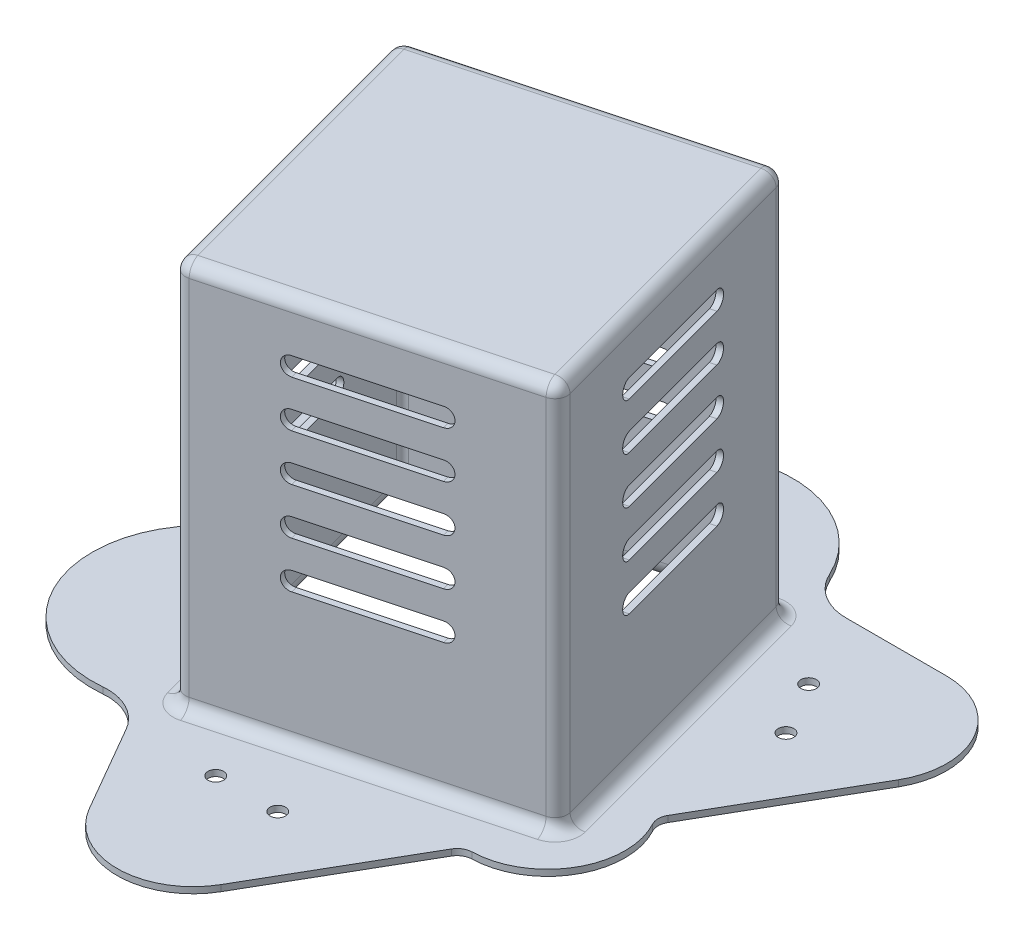
SolidWorks part; units mm, degrees
material "AISI 316 Stainless Steel Sheet (SS)"
ref_plane "Front" through (0, 0, 0) normal (0, 0, 1) x (1, 0, 0)
ref_plane "Top" through (0, 0, 0) normal (0, 1, 0) x (1, 0, 0)
ref_plane "Right" through (0, 0, 0) normal (1, 0, 0) x (0, 0, -1)
sketch "Sketch1" plane through (0, 0, 0) normal (0, 1, 0) x (1, 0, 0)
  line L0 (-50.8, 51.1378) -> (50.8, 51.1378)
  line L1 (0, 51.1378) -> (0, 0) construction
  line L2 (63.1733, 29.7066) -> (12.3733, -58.2816)
  line L3 (0, 0) -> (0, -51.1378) construction
  line L4 (-12.3733, -58.2816) -> (-63.1733, 29.7066)
  arc A0 (-50.8, 51.1378) -> (-63.1733, 29.7066) centre (-50.8, 36.8503) ccw
  arc A1 (63.1733, 29.7066) -> (50.8, 51.1378) centre (50.8, 36.8503) ccw
  arc A2 (-12.3733, -58.2816) -> (12.3733, -58.2816) centre (0, -51.1378) ccw
  dimension "D2" = 28.575
  dimension "D1" = 101.6
extrude "Boss-Extrude1" add sketch "Sketch1" along normal blind 12.7
hole_wizard "1/2-13 Tapped Hole1" positions "Sketch2" profile "Sketch3" tap size "1/2-13" standard "ANSI Inch" end condition through all
sketch "Sketch2" plane through (0, 12.7, 0) normal (0, 1, 0) x (1, 0, 0)
  point P0 (-50.8, 36.8503)
  point P3 (0, -51.1378)
  point P6 (50.8, 36.8503)
sketch "Sketch3" plane through (-50.8, 12.7, -36.8503) normal (1, 0, 0) x (0, 0, 1)
  line L0 (0, 0) -> (0, 12.7)
  line L1 (0, 12.7) -> (5.3581, 12.7)
  line L2 (5.3581, 12.7) -> (5.3581, 0)
  line L5 (5.3581, 0) -> (0, 0)
  line L11 (0, -6.35) -> (0, 107.95) construction
  dimension "Thru Tap Drill Dia." = 10.7163
  dimension "Thru Tap Drill Depth" = 12.7
cosmetic thread "Hole Thread1" parameters "D2"=12.7
cosmetic thread "Hole Thread2" parameters "D2"=12.7
cosmetic thread "Hole Thread3" parameters "D2"=12.7
sketch "Sketch7" plane through (0, 12.7, 0) normal (0, 1, 0) x (1, 0, 0)
  line L0 (12.3733, -58.2816) -> (63.1733, 29.7066)
  line L1 (30.1863, 42.2085) -> (-30.1863, 42.2085)
  line L3 (-50.8, 36.8503) -> (37.7733, -14.2875) construction
  line L5 (-14.9471, -35.965) -> (-45.1335, 16.3193)
  line L7 (56.1581, 36.8503) -> (65.0875, 36.8503) construction
  line L8 (30.1863, 42.2085) -> (30.1863, 51.1378) construction
  line L10 (50.8, 51.1378) -> (-50.8, 51.1378) construction
  line L11 (12.3733, -58.2816) -> (63.1733, 29.7066) construction
  arc A0 (63.1733, 29.7066) -> (36.529, 36.1637) centre (50.8, 36.8503) cw
  arc A1 (36.529, 36.1637) -> (30.1863, 42.2085) centre (30.1863, 35.8585) ccw
  arc A2 (-36.529, 36.1637) -> (-43.0698, 24.8346) centre (-50.8, 36.8503) cw
  arc A3 (-36.529, 36.1637) -> (-30.1863, 42.2085) centre (-30.1863, 35.8585) cw
  arc A6 (-6.5408, -38.4355) -> (-14.9471, -35.965) centre (-9.4478, -32.79) cw
  arc A7 (12.3733, -58.2816) -> (-6.5408, -38.4355) centre (0, -51.1378) ccw
  arc A8 (-43.0698, 24.8346) -> (-45.1335, 16.3193) centre (-39.6342, 19.4943) ccw
  circle A10 centre (-50.8, 36.8503) radius 5.3581 construction
  arc A11 (63.1733, 29.7066) -> (50.8, 51.1378) centre (50.8, 36.8503) ccw construction
  circle A12 centre (50.8, 36.8503) radius 5.3581 construction
  dimension "D1" = 6.35
extrude "Cut-Extrude1" cut sketch "Sketch7" against normal through all
sketch "Sketch10" plane through (0, 12.7, 0) normal (0, 1, 0) x (1, 0, 0)
  line L0 (-63.1733, 29.7066) -> (-12.3733, -58.2816) construction
  line L2 (-45.1335, 16.3193) -> (-14.9471, -35.965) construction
  line L7 (-54.4981, -23.9435) -> (-46.765, -19.4789) construction
  line L8 (-50.8, 36.8503) -> (-35.7665, -13.1289) construction
  line L9 (-35.7665, -13.1289) -> (0, -51.1378) construction
  line L10 (-35.7665, -13.1289) -> (0, 0) construction
  line L11 (-45.1335, 16.3193) -> (-14.9471, -35.965)
  line L12 (-52.8665, 11.8546) -> (-22.6802, -40.4296)
  circle A0 centre (-35.7665, -13.1289) radius 12.7
  arc A2 (-52.8665, 11.8546) -> (-53.4367, -0.6551) centre (-62.9285, 6.0454) cw
  arc A3 (-53.4367, -0.6551) -> (-33.799, -34.6686) centre (-35.7665, -13.1289) ccw
  arc A4 (-33.799, -34.6686) -> (-22.6802, -40.4296) centre (-32.7421, -46.2389) cw
  arc A5 (-34.6112, -25.7762) -> (-14.9471, -35.965) centre (-32.7421, -46.2389) cw
  arc A6 (-46.1418, -5.8047) -> (-45.1335, 16.3193) centre (-62.9285, 6.0454) ccw
  line M11 (-63.1733, 29.7066) -> (-12.3733, -58.2816)
  line M14 (-14.9471, -35.965) -> (-45.1335, 16.3193)
  dimension "D1" = 38.1
  dimension "D2" = 25.4
extrude "Boss-Extrude2" add sketch "Sketch10" against normal up to surface (12.7 mm away) contours A0 A6 A2 A3 A4 L12 A5 M11 region at (-45.7457, 12.7, 4.0329) up to face at (-12.6339, 0, -14.8151)
extrude "Cut-Extrude2" cut sketch "Sketch10<3>" against normal through all contours A6 L12 A0 M14 | L12 A0 L11 | A5 A0 M11 M14 region at (-40.5923, 12.7, -3.1335) region at (-33.9909, 12.7, 12.1037) region at (-24.0958, 12.7, 25.4392)
sketch "Sketch10<3>" plane through (0, 12.7, 0) normal (0, 1, 0) x (1, 0, 0) same geometry as "Sketch10"
hole_wizard "#4-40 Tapped Hole1" positions "Sketch8" profile "Sketch9" tap size "#4-40" standard "ANSI Inch"
sketch "Sketch8" plane through (-34.5167, 0, 19.9282) normal (-0.866, 0, 0.5) x (0.5, 0, 0.866)
  line L4 (-50.9633, 6.35) -> (-6.5133, 6.35) construction
  line L5 (-6.5133, 6.35) -> (37.9367, 6.35) construction
  line L8 (-57.3133, 12.7) -> (44.2867, 12.7) construction
  line L9 (-57.3133, 12.7) -> (-36.6997, 12.7) construction
  line L11 (44.2867, 12.7) -> (44.2867, 0) construction
  line L12 (-57.3133, 12.7) -> (-57.3133, 0) construction
  point P0 (-50.9633, 6.35)
  point P2 (37.9367, 6.35)
  point P34 (-6.5133, 12.7)
  point P43 (-57.3133, 6.35)
  dimension "D1" = 44.45
sketch "Sketch9" plane through (-59.9983, 6.35, -24.2073) normal (0, 1, 0) x (0.5, 0, 0.866)
  line L0 (0, 0) -> (0, 8.6167)
  line L1 (0, 8.6167) -> (1.1303, 7.9375)
  line L2 (1.1303, 7.9375) -> (1.1303, 0)
  line L5 (1.1303, 0) -> (0, 0)
  line L10 (0, 8.6167) -> (-1.1303, 7.9375) construction
  line L11 (0, -6.35) -> (0, 107.95) construction
  dimension "Tap Drill Dia." = 2.2606
  dimension "Tap Drill Depth" = 7.9375
  dimension "Drill Angle" = 118
cosmetic thread "Hole Thread4" parameters "D1"=6.35, "D2"=2.8448
cosmetic thread "Hole Thread5" parameters "D1"=6.35, "D2"=2.8448
ref_plane "Plane1" through (3.2567, 0, -5.6407) normal (-0.5, 0, 0.866) x (0.866, 0, 0.5)
mirror "Mirror1" about plane through (3.2567, 0, -5.6407) normal (-0.5, 0, 0.866) of "Cut-Extrude2", "Boss-Extrude2", "#4-40 Tapped Hole1"
cosmetic thread "Hole Thread6" parameters "D1"=6.35, "D2"=2.8448
cosmetic thread "Hole Thread7" parameters "D1"=6.35, "D2"=2.8448
chamfer "Chamfer3" distance 1.27 angle 45 54 edges at (50.8, 0, -31.4922) (0, 0, 56.496) (-50.8, 0, -31.4922) (-40.4932, 0, -51.1378) (40.4932, 0, -51.1378) (-63.1733, 0, -43.9941) (-17.5268, 0, 49.3556) (-58.0199, 0, -20.7806) (13.7078, 0, 55.1664) (-11.2383, 0, 38.8823) (-45.8056, 0, -20.9899) (-38.4267, 0, -29.7066) (-34.5672, 0, -40.4552) (34.5672, 0, -40.4552) (61.1427, 0, -26.9933) (50.8, 12.7, -31.4922) (0, 12.7, 56.496) (-50.8, 12.7, -31.4922) (-34.5672, 12.7, -40.4552) (-38.4267, 12.7, -29.7066) (-45.8056, 12.7, -20.9899) (-11.2383, 12.7, 38.8823) (13.7078, 12.7, 55.1664) (-58.0199, 12.7, -20.7806) (-17.5268, 12.7, 49.3556) (-63.1733, 12.7, -43.9941) (40.4932, 12.7, -51.1378) (-40.4932, 12.7, -51.1378) (61.1427, 12.7, -26.9933) (34.5672, 12.7, -40.4552) (-46.765, 12.7, 19.4789) (-23.289, 12.7, 27.9946) (-27.397, 12.7, 35.9229) (-54.4981, 12.7, 23.9435) (-51.322, 12.7, -5.5164) (-42.4019, 12.7, -5.1098) (-23.925, 12.7, -52.9694) (0, 12.7, -70.4499) (23.925, 12.7, -52.9694) (19.1129, 12.7, -45.4476) (0, 12.7, -61.5206) (-19.1129, 12.7, -45.4476) (0, 0, -61.5206) (19.1129, 0, -45.4476) (23.925, 0, -52.9694) (0, 0, -70.4499) (-23.925, 0, -52.9694) (-51.322, 0, -5.5164) (-54.4981, 0, 23.9435) (-27.397, 0, 35.9229) (-23.289, 0, 27.9946) (-46.765, 0, 19.4789) (-42.4019, 0, -5.1098) (-19.1129, 0, -45.4476)
sketch "Sketch11" plane through (0, 12.7, 0) normal (0, 1, 0) x (1, 0, 0)
  line L0 (-12.3733, -58.2816) -> (-22.6802, -40.4296) construction
  line L1 (-52.8665, 11.8546) -> (-63.1733, 29.7066) construction
  line L2 (-50.8, 51.1378) -> (-30.1863, 51.1378) construction
  line L3 (30.1863, 51.1378) -> (50.8, 51.1378) construction
  line L4 (-12.3733, -58.2816) -> (-22.6802, -40.4296)
  line L5 (-52.8665, 11.8546) -> (-63.1733, 29.7066)
  line L6 (-50.8, 51.1378) -> (-30.1863, 51.1378)
  line L7 (30.1863, 51.1378) -> (50.8, 51.1378)
  line L8 (-13.4732, -58.9166) -> (-23.78, -41.0646)
  line L9 (-53.9664, 11.2196) -> (-64.2732, 29.0716)
  line L10 (-50.8, 52.4078) -> (-30.1863, 52.4078)
  line L11 (30.1863, 52.4078) -> (50.8, 52.4078)
  line L12 (12.3733, -58.2816) -> (13.4732, -58.9166)
  line L13 (0, 0) -> (-50.8, 36.8503) construction
  line L14 (63.1733, 29.7066) -> (64.2732, 29.0716)
  line L15 (64.2732, 29.0716) -> (13.4732, -58.9166)
  arc A0 (-12.3733, -58.2816) -> (-6.5408, -38.4355) centre (0, -51.1378) ccw construction
  arc A1 (-22.6802, -40.4296) -> (-33.799, -34.6686) centre (-32.7421, -46.2389) ccw construction
  arc A2 (-53.4367, -0.6551) -> (-33.799, -34.6686) centre (-35.7665, -13.1289) ccw construction
  arc A3 (-53.4367, -0.6551) -> (-52.8665, 11.8546) centre (-62.9285, 6.0454) ccw construction
  arc A4 (-50.8, 51.1378) -> (-63.1733, 29.7066) centre (-50.8, 36.8503) ccw construction
  arc A5 (-30.1863, 51.1378) -> (-19.6377, 57.8865) centre (-30.1863, 62.7564) ccw construction
  arc A6 (19.6377, 57.8865) -> (-19.6377, 57.8865) centre (0, 48.8206) ccw construction
  arc A7 (19.6377, 57.8865) -> (30.1863, 51.1378) centre (30.1863, 62.7564) ccw construction
  arc A8 (36.529, 36.1637) -> (50.8, 51.1378) centre (50.8, 36.8503) ccw construction
  arc A9 (-12.3733, -58.2816) -> (12.3733, -58.2816) centre (0, -51.1378) ccw
  arc A10 (-22.6802, -40.4296) -> (-33.799, -34.6686) centre (-32.7421, -46.2389) ccw
  arc A11 (-53.4367, -0.6551) -> (-33.799, -34.6686) centre (-35.7665, -13.1289) ccw
  arc A12 (-53.4367, -0.6551) -> (-52.8665, 11.8546) centre (-62.9285, 6.0454) ccw
  arc A13 (-50.8, 51.1378) -> (-63.1733, 29.7066) centre (-50.8, 36.8503) ccw
  arc A14 (-30.1863, 51.1378) -> (-19.6377, 57.8865) centre (-30.1863, 62.7564) ccw
  arc A15 (19.6377, 57.8865) -> (-19.6377, 57.8865) centre (0, 48.8206) ccw
  arc A16 (19.6377, 57.8865) -> (30.1863, 51.1378) centre (30.1863, 62.7564) ccw
  arc A17 (63.1733, 29.7066) -> (50.8, 51.1378) centre (50.8, 36.8503) ccw
  arc A18 (-13.4732, -58.9166) -> (13.4732, -58.9166) centre (0, -51.1378) ccw
  arc A19 (-23.78, -41.0646) -> (-33.6835, -35.9333) centre (-32.7421, -46.2389) ccw
  arc A20 (-54.4742, 0.0773) -> (-33.6835, -35.9333) centre (-35.7665, -13.1289) ccw
  arc A21 (-54.4742, 0.0773) -> (-53.9664, 11.2196) centre (-62.9285, 6.0454) ccw
  arc A22 (-50.8, 52.4078) -> (-64.2732, 29.0716) centre (-50.8, 36.8503) ccw
  arc A23 (-30.1863, 52.4078) -> (-20.7907, 58.4188) centre (-30.1863, 62.7564) ccw
  arc A24 (20.7907, 58.4188) -> (-20.7907, 58.4188) centre (0, 48.8206) ccw
  arc A25 (20.7907, 58.4188) -> (30.1863, 52.4078) centre (30.1863, 62.7564) ccw
  arc A26 (64.2732, 29.0716) -> (50.8, 52.4078) centre (50.8, 36.8503) ccw
  arc A27 (-13.4732, -58.9166) -> (-7.1222, -37.3064) centre (0, -51.1378) ccw construction
  arc A28 (-12.3733, -58.2816) -> (-6.5408, -38.4355) centre (0, -51.1378) ccw construction
  arc A29 (35.2605, 36.1026) -> (50.8, 52.4078) centre (50.8, 36.8503) ccw construction
  arc A30 (36.529, 36.1637) -> (50.8, 51.1378) centre (50.8, 36.8503) ccw construction
  circle M4 centre (50.8, 36.8503) radius 6.6281
  circle M5 centre (0, -51.1378) radius 6.6281
  circle M6 centre (-50.8, 36.8503) radius 6.6281
  arc M7 (-46.2333, 15.6843) -> (-43.757, 25.9027) centre (-39.6342, 19.4943) cw
  arc M8 (-43.757, 25.9027) -> (-37.7975, 36.2247) centre (-50.8, 36.8503) ccw
  arc M9 (-37.7975, 36.2247) -> (-30.1863, 43.4785) centre (-30.1863, 35.8585) cw
  arc M10 (-30.1863, 43.4785) -> (-12.6836, 54.6761) centre (-30.1863, 62.7564) ccw
  arc M11 (-12.6836, 54.6761) -> (12.6836, 54.6761) centre (0, 48.8206) cw
  arc M12 (12.6836, 54.6761) -> (30.1863, 43.4785) centre (30.1863, 62.7564) ccw
  arc M13 (30.1863, 43.4785) -> (37.7975, 36.2247) centre (30.1863, 35.8585) cw
  arc M14 (37.7975, 36.2247) -> (50.8, 49.8678) centre (50.8, 36.8503) ccw
  line M15 (50.8, 49.8678) -> (30.1863, 49.8678)
  arc M16 (30.1863, 49.8678) -> (18.4846, 57.3542) centre (30.1863, 62.7564) cw
  arc M17 (18.4846, 57.3542) -> (-18.4846, 57.3542) centre (0, 48.8206) ccw
  arc M18 (-18.4846, 57.3542) -> (-30.1863, 49.8678) centre (-30.1863, 62.7564) cw
  line M19 (-30.1863, 49.8678) -> (-50.8, 49.8678)
  arc M20 (-50.8, 49.8678) -> (-62.0735, 30.3416) centre (-50.8, 36.8503) ccw
  line M21 (-62.0735, 30.3416) -> (-51.7667, 12.4896)
  arc M22 (-51.7667, 12.4896) -> (-52.3991, -1.3875) centre (-62.9285, 6.0454) cw
  arc M23 (-52.3991, -1.3875) -> (-33.9145, -33.4038) centre (-35.7665, -13.1289) ccw
  arc M24 (-33.9145, -33.4038) -> (-21.5803, -39.7946) centre (-32.7421, -46.2389) cw
  line M25 (-21.5803, -39.7946) -> (-11.2735, -57.6466)
  arc M26 (-11.2735, -57.6466) -> (-5.9594, -39.5646) centre (0, -51.1378) ccw
  arc M27 (-5.9594, -39.5646) -> (-16.047, -36.6) centre (-9.4478, -32.79) cw
  arc M28 (-16.047, -36.6) -> (-34.4957, -27.0409) centre (-32.7421, -46.2389) ccw
  arc M29 (-34.4957, -27.0409) -> (-47.1793, -5.0723) centre (-35.7665, -13.1289) cw
  arc M30 (-47.1793, -5.0723) -> (-46.2333, 15.6843) centre (-62.9285, 6.0454) ccw
  dimension "D1" = 1.27
extrude "Boss-Extrude3" add sketch "Sketch11" against normal blind 609.6 separate body contours L14 A26 L11 A25 A24 A23 L10 A22 L9 A21 A20 A19 L8 A18 L12 A9 L4 A10 A11 A12 L5 A13 L6 A14 A15 A16 L7 A17 region at (0, 12.7, 65.6171)
extrude "Cut-Extrude3" cut sketch "Sketch11<4>" against normal through all contours L14 A17 L7 A16 A15 A14 L6 A13 L5 A12 A11 A10 L4 A9 L12 L15 M7 M30 M29 M28 M27 M26 M25 M24 M23 M22 M21 M20 M19 M18 M17 M16 M15 M14 M13 M12 M11 M10 M9 M8 | M30 M7 M8 M9 M10 M11 M12 M13 M14 M15 M16 M17 M18 M19 M20 M21 M22 M23 M24 M25 M26 M27 M28 M29 M5 M6 M4 | M6 | M4 | M5 region at (0.316, 12.7, -7.3385) region at (50.8, 12.7, -36.8503) region at (0, 12.7, 51.1378) region at (-50.8, 12.7, -36.8503) region at (-45.5144, 12.7, -5.2517)
sketch "Sketch11<4>" plane through (0, 12.7, 0) normal (0, 1, 0) x (1, 0, 0) same geometry as "Sketch11"
hole_wizard "#4 Clearance Hole1" positions "Sketch12" profile "Sketch13" hole size "#4" standard "ANSI Inch"
sketch "Sketch12" plane through (-35.6165, 0, 20.5632) normal (-0.866, 0, 0.5) x (0.5, 0, 0.866)
  line L0 (44.2867, -596.9) -> (23.673, -596.9) construction
  line L2 (44.2867, -596.9) -> (44.2867, 12.7) construction
  line L3 (-57.3133, -596.9) -> (-57.3133, 12.7) construction
  line L4 (-36.6997, -596.9) -> (-57.3133, -596.9) construction
  line L5 (44.2867, 12.7) -> (23.673, 12.7) construction
  line L6 (-36.6997, 12.7) -> (-57.3133, 12.7) construction
  line L7 (14.2774, 12.7) -> (-27.3041, 12.7) construction
  point P0 (37.9367, 6.35)
  point P2 (-50.9633, 6.35)
  point P4 (37.9367, -273.05)
  point P6 (-50.9633, -273.05)
  point P8 (-50.9633, -590.55)
  point P10 (37.9367, -590.55)
  dimension "D1" = 6.35
  dimension "D2" = 6.35
  dimension "D3" = 6.35
  dimension "D4" = 6.35
  dimension "D5" = 6.35
  dimension "D6" = 6.35
  dimension "D7" = 6.35
  dimension "D8" = 6.35
  dimension "D9" = 6.35
  dimension "D10" = 285.75
  dimension "D11" = 6.35
sketch "Sketch13" plane through (-16.6482, 6.35, 53.4173) normal (0, 1, 0) x (0.5, 0, 0.866)
  line L0 (0, 0) -> (0, 7.3306)
  line L1 (0, 7.3306) -> (1.6319, 6.35)
  line L2 (1.6319, 6.35) -> (1.6319, 0)
  line L5 (1.6319, 0) -> (0, 0)
  line L10 (0, 7.3306) -> (-1.6319, 6.35) construction
  line L11 (0, -6.35) -> (0, 107.95) construction
  dimension "Hole Dia." = 3.2639
  dimension "Hole Depth" = 6.35
  dimension "Drill Angle" = 118
mirror "Mirror2" about plane through (3.2567, 0, -5.6407) normal (-0.5, 0, 0.866) of "#4 Clearance Hole1"
sketch "Sketch14" plane through (0, 12.7, 0) normal (0, 1, 0) x (1, 0, 0)
  line L0 (13.4732, -58.9166) -> (64.2732, 29.0716)
  line L1 (-63.1733, 29.7066) -> (-12.3733, -58.2816) construction
  line L10 (63.1733, 29.7066) -> (64.2732, 29.0716)
  line L11 (50.8, 52.4078) -> (30.1863, 52.4078)
  line L12 (-30.1863, 52.4078) -> (-50.8, 52.4078)
  line L13 (-64.2732, 29.0716) -> (-53.9664, 11.2196)
  line L14 (-23.78, -41.0646) -> (-13.4732, -58.9166)
  line L15 (13.4732, -58.9166) -> (12.3733, -58.2816)
  line L16 (-12.3733, -58.2816) -> (-22.6802, -40.4296)
  line L17 (-52.8665, 11.8546) -> (-63.1733, 29.7066)
  line L18 (-50.8, 51.1378) -> (-30.1863, 51.1378)
  line L19 (30.1863, 51.1378) -> (50.8, 51.1378)
  line L20 (63.1733, 29.7066) -> (64.2732, 29.0716)
  line L21 (50.8, 52.4078) -> (30.1863, 52.4078)
  line L22 (-30.1863, 52.4078) -> (-50.8, 52.4078)
  line L23 (-64.2732, 29.0716) -> (-53.9664, 11.2196)
  line L24 (-23.78, -41.0646) -> (-13.4732, -58.9166)
  line L25 (13.4732, -58.9166) -> (12.3733, -58.2816)
  line L26 (-12.3733, -58.2816) -> (-22.6802, -40.4296)
  line L27 (-52.8665, 11.8546) -> (-63.1733, 29.7066)
  line L28 (-50.8, 51.1378) -> (-30.1863, 51.1378)
  line L29 (30.1863, 51.1378) -> (50.8, 51.1378)
  arc A18 (64.2732, 29.0716) -> (50.8, 52.4078) centre (50.8, 36.8503) ccw
  arc A19 (20.7907, 58.4188) -> (30.1863, 52.4078) centre (30.1863, 62.7564) ccw
  arc A20 (20.7907, 58.4188) -> (-20.7907, 58.4188) centre (0, 48.8206) ccw
  arc A21 (-30.1863, 52.4078) -> (-20.7907, 58.4188) centre (-30.1863, 62.7564) ccw
  arc A22 (-50.8, 52.4078) -> (-64.2732, 29.0716) centre (-50.8, 36.8503) ccw
  arc A23 (-54.4742, 0.0773) -> (-53.9664, 11.2196) centre (-62.9285, 6.0454) ccw
  arc A24 (-54.4742, 0.0773) -> (-33.6835, -35.9333) centre (-35.7665, -13.1289) ccw
  arc A25 (-23.78, -41.0646) -> (-33.6835, -35.9333) centre (-32.7421, -46.2389) ccw
  arc A26 (-13.4732, -58.9166) -> (13.4732, -58.9166) centre (0, -51.1378) ccw
  arc A27 (-12.3733, -58.2816) -> (12.3733, -58.2816) centre (0, -51.1378) ccw
  arc A28 (-22.6802, -40.4296) -> (-33.799, -34.6686) centre (-32.7421, -46.2389) ccw
  arc A29 (-53.4367, -0.6551) -> (-33.799, -34.6686) centre (-35.7665, -13.1289) ccw
  arc A30 (-53.4367, -0.6551) -> (-52.8665, 11.8546) centre (-62.9285, 6.0454) ccw
  arc A31 (-50.8, 51.1378) -> (-63.1733, 29.7066) centre (-50.8, 36.8503) ccw
  arc A32 (-30.1863, 51.1378) -> (-19.6377, 57.8865) centre (-30.1863, 62.7564) ccw
  arc A33 (19.6377, 57.8865) -> (-19.6377, 57.8865) centre (0, 48.8206) ccw
  arc A34 (19.6377, 57.8865) -> (30.1863, 51.1378) centre (30.1863, 62.7564) ccw
  arc A35 (63.1733, 29.7066) -> (50.8, 51.1378) centre (50.8, 36.8503) ccw
  arc A36 (64.2732, 29.0716) -> (50.8, 52.4078) centre (50.8, 36.8503) ccw
  arc A37 (20.7907, 58.4188) -> (30.1863, 52.4078) centre (30.1863, 62.7564) ccw
  arc A38 (20.7907, 58.4188) -> (-20.7907, 58.4188) centre (0, 48.8206) ccw
  arc A39 (-30.1863, 52.4078) -> (-20.7907, 58.4188) centre (-30.1863, 62.7564) ccw
  arc A40 (-50.8, 52.4078) -> (-64.2732, 29.0716) centre (-50.8, 36.8503) ccw
  arc A41 (-54.4742, 0.0773) -> (-53.9664, 11.2196) centre (-62.9285, 6.0454) ccw
  arc A42 (-54.4742, 0.0773) -> (-33.6835, -35.9333) centre (-35.7665, -13.1289) ccw
  arc A43 (-23.78, -41.0646) -> (-33.6835, -35.9333) centre (-32.7421, -46.2389) ccw
  arc A44 (-13.4732, -58.9166) -> (13.4732, -58.9166) centre (0, -51.1378) ccw
  arc A45 (-12.3733, -58.2816) -> (12.3733, -58.2816) centre (0, -51.1378) ccw
  arc A46 (-22.6802, -40.4296) -> (-33.799, -34.6686) centre (-32.7421, -46.2389) ccw
  arc A47 (-53.4367, -0.6551) -> (-33.799, -34.6686) centre (-35.7665, -13.1289) ccw
  arc A48 (-53.4367, -0.6551) -> (-52.8665, 11.8546) centre (-62.9285, 6.0454) ccw
  arc A49 (-50.8, 51.1378) -> (-63.1733, 29.7066) centre (-50.8, 36.8503) ccw
  arc A50 (-30.1863, 51.1378) -> (-19.6377, 57.8865) centre (-30.1863, 62.7564) ccw
  arc A51 (19.6377, 57.8865) -> (-19.6377, 57.8865) centre (0, 48.8206) ccw
  arc A52 (19.6377, 57.8865) -> (30.1863, 51.1378) centre (30.1863, 62.7564) ccw
  arc A53 (63.1733, 29.7066) -> (50.8, 51.1378) centre (50.8, 36.8503) ccw
  line M31 (63.1733, 29.7066) -> (64.2732, 29.0716)
  arc M32 (64.2732, 29.0716) -> (50.8, 52.4078) centre (50.8, 36.8503) ccw
  line M33 (50.8, 52.4078) -> (30.1863, 52.4078)
  arc M34 (30.1863, 52.4078) -> (20.7907, 58.4188) centre (30.1863, 62.7564) cw
  arc M35 (20.7907, 58.4188) -> (-20.7907, 58.4188) centre (0, 48.8206) ccw
  arc M36 (-20.7907, 58.4188) -> (-30.1863, 52.4078) centre (-30.1863, 62.7564) cw
  line M37 (-30.1863, 52.4078) -> (-50.8, 52.4078)
  arc M38 (-50.8, 52.4078) -> (-64.2732, 29.0716) centre (-50.8, 36.8503) ccw
  line M39 (-64.2732, 29.0716) -> (-53.9664, 11.2196)
  arc M40 (-53.9664, 11.2196) -> (-54.4742, 0.0773) centre (-62.9285, 6.0454) cw
  arc M41 (-54.4742, 0.0773) -> (-33.6835, -35.9333) centre (-35.7665, -13.1289) ccw
  arc M42 (-33.6835, -35.9333) -> (-23.78, -41.0646) centre (-32.7421, -46.2389) cw
  line M43 (-23.78, -41.0646) -> (-13.4732, -58.9166)
  arc M44 (-13.4732, -58.9166) -> (13.4732, -58.9166) centre (0, -51.1378) ccw
  line M45 (13.4732, -58.9166) -> (12.3733, -58.2816)
  arc M46 (12.3733, -58.2816) -> (-12.3733, -58.2816) centre (0, -51.1378) cw
  line M47 (-12.3733, -58.2816) -> (-22.6802, -40.4296)
  arc M48 (-22.6802, -40.4296) -> (-33.799, -34.6686) centre (-32.7421, -46.2389) ccw
  arc M49 (-33.799, -34.6686) -> (-53.4367, -0.6551) centre (-35.7665, -13.1289) cw
  arc M50 (-53.4367, -0.6551) -> (-52.8665, 11.8546) centre (-62.9285, 6.0454) ccw
  line M51 (-52.8665, 11.8546) -> (-63.1733, 29.7066)
  arc M52 (-63.1733, 29.7066) -> (-50.8, 51.1378) centre (-50.8, 36.8503) cw
  line M53 (-50.8, 51.1378) -> (-30.1863, 51.1378)
  arc M54 (-30.1863, 51.1378) -> (-19.6377, 57.8865) centre (-30.1863, 62.7564) ccw
  arc M55 (-19.6377, 57.8865) -> (19.6377, 57.8865) centre (0, 48.8206) cw
  arc M56 (19.6377, 57.8865) -> (30.1863, 51.1378) centre (30.1863, 62.7564) ccw
  line M57 (30.1863, 51.1378) -> (50.8, 51.1378)
  arc M58 (50.8, 51.1378) -> (63.1733, 29.7066) centre (50.8, 36.8503) cw
  dimension "D1" = 0
extrude "Boss-Extrude4" add sketch "Sketch14" along normal blind 1.27 contours L1 L0 M51 M47 M46 M45 M31 M58 M57 M56 M55 M54 M53 M52 | M58 M31 M32 M33 M34 M35 M36 M37 M38 M39 M40 M41 M42 M43 M44 M45 M46 M47 M48 M49 M50 M51 M52 M53 M54 M55 M56 M57 | L1 M50 M49 M48 region at (0.4822, 12.7, -10.555) region at (0, 12.7, 66.5036) region at (-44.5953, 12.7, 18.2261)
extrude "Cut-Extrude4" cut sketch "Sketch14<3>" against normal through all contours L1 M50 M49 M48 | L1 L0 M51 M47 M46 M45 M31 M58 M57 M56 M55 M54 M53 M52 | M58 M31 M32 M33 M34 M35 M36 M37 M38 M39 M40 M41 M42 M43 M44 M45 M46 M47 M48 M49 M50 M51 M52 M53 M54 M55 M56 M57 region at (0.4822, 12.7, -10.555) region at (0, 12.7, 66.5036) region at (-44.5953, 12.7, 18.2261)
sketch "Sketch14<3>" plane through (0, 12.7, 0) normal (0, 1, 0) x (1, 0, 0) same geometry as "Sketch14"
sketch "Sketch19" plane through (0, 13.97, 0) normal (0, 1, 0) x (1, 0, 0)
  line L0 (32.989, -11.5253) -> (-50.8, 36.8503) construction
  line L1 (13.4732, -58.9166) -> (64.2732, 29.0716) construction
  line L2 (38.8732, -14.9225) -> (32.989, -11.5253) construction
  circle A0 centre (32.989, -11.5253) radius 15.875
  arc A1 (-50.8, 52.4078) -> (-64.2732, 29.0716) centre (-50.8, 36.8503) ccw construction
  dimension "D2" = 31.75
  dimension "D1" = 6.7945
extrude "Boss-Extrude6" add sketch "Sketch19" against normal blind 1.27
sketch "Sketch15" plane through (0, 13.97, 0) normal (0, 1, 0) x (1, 0, 0)
  line L0 (-39.6634, 30.4206) -> (-22.8997, -32.1424)
  line L1 (-39.6634, 30.4206) -> (22.8997, 47.1843)
  line L2 (-22.8997, -32.1424) -> (39.6634, -15.3787)
  line L3 (22.8997, 47.1843) -> (39.6634, -15.3787)
  line L4 (22.8997, 47.1843) -> (-22.8997, -32.1424) construction
  line L5 (39.6634, -15.3787) -> (0, 7.5209) construction
  line L6 (-50.8, 36.8503) -> (0, 7.5209) construction
  line L7 (0, 7.5209) -> (0, -51.1378) construction
  line L8 (0, 7.5209) -> (50.8, 36.8503) construction
  dimension "D1" = 64.77
extrude "Boss-Extrude5" add sketch "Sketch15" along normal blind 79.375
fillet "Fillet1" radius 2.54 12 edges at (-31.2815, 13.97, 0.8609) (8.3819, 13.97, 23.7606) (-8.3819, 13.97, -38.8025) (31.2815, 93.345, -15.9028) (8.3819, 93.345, 23.7606) (-31.2815, 93.345, 0.8609) (-8.3819, 93.345, -38.8025) (31.2815, 13.97, -15.9028) (22.8997, 53.6575, -47.1843) (39.6634, 53.6575, 15.3787) (-39.6634, 53.6575, -30.4206) (-22.8997, 53.6575, 32.1424)
shell "Shell1" thickness 1.27 removed face at (-5.5895, 12.7, -10.7481)
sketch "Sketch16" plane through (33.1617, 0, -8.8857) normal (0.9659, 0, -0.2588) x (-0.2588, 0, -0.9659)
  line L0 (-5.4353, 81.28) -> (19.9647, 81.28) construction
  line L1 (-5.4353, 83.185) -> (19.9647, 83.185)
  line L2 (-5.4353, 79.375) -> (19.9647, 79.375)
  line L3 (-5.4353, 71.755) -> (19.9647, 71.755) construction
  line L4 (-5.4353, 73.66) -> (19.9647, 73.66)
  line L5 (-5.4353, 69.85) -> (19.9647, 69.85)
  line L6 (-5.4353, 62.23) -> (19.9647, 62.23) construction
  line L7 (-5.4353, 64.135) -> (19.9647, 64.135)
  line L8 (-5.4353, 60.325) -> (19.9647, 60.325)
  line L9 (-5.4353, 52.705) -> (19.9647, 52.705) construction
  line L10 (-5.4353, 54.61) -> (19.9647, 54.61)
  line L11 (-5.4353, 50.8) -> (19.9647, 50.8)
  line L12 (-5.4353, 43.18) -> (19.9647, 43.18) construction
  line L13 (-5.4353, 45.085) -> (19.9647, 45.085)
  line L14 (-5.4353, 41.275) -> (19.9647, 41.275)
  line L15 (7.2647, 90.805) -> (7.2647, 81.28) construction
  line L16 (37.1097, 90.805) -> (-22.5803, 90.805) construction
  line L17 (7.2647, 81.28) -> (7.2647, 71.755) construction
  line L18 (7.2647, 71.755) -> (7.2647, 62.23) construction
  line L19 (7.2647, 62.23) -> (7.2647, 52.705) construction
  line L20 (7.2647, 52.705) -> (7.2647, 43.18) construction
  arc A0 (-5.4353, 83.185) -> (-5.4353, 79.375) centre (-5.4353, 81.28) ccw
  arc A1 (19.9647, 79.375) -> (19.9647, 83.185) centre (19.9647, 81.28) ccw
  arc A2 (-5.4353, 73.66) -> (-5.4353, 69.85) centre (-5.4353, 71.755) ccw
  arc A3 (19.9647, 69.85) -> (19.9647, 73.66) centre (19.9647, 71.755) ccw
  arc A4 (-5.4353, 64.135) -> (-5.4353, 60.325) centre (-5.4353, 62.23) ccw
  arc A5 (19.9647, 60.325) -> (19.9647, 64.135) centre (19.9647, 62.23) ccw
  arc A6 (-5.4353, 54.61) -> (-5.4353, 50.8) centre (-5.4353, 52.705) ccw
  arc A7 (19.9647, 50.8) -> (19.9647, 54.61) centre (19.9647, 52.705) ccw
  arc A8 (-5.4353, 45.085) -> (-5.4353, 41.275) centre (-5.4353, 43.18) ccw
  arc A9 (19.9647, 41.275) -> (19.9647, 45.085) centre (19.9647, 43.18) ccw
  point P2 (7.2647, 81.28)
  point P7 (7.2647, 71.755)
  point P14 (7.2647, 62.23)
  point P21 (7.2647, 52.705)
  point P28 (7.2647, 43.18)
  dimension "D1" = 25.4
  dimension "D2" = 9.525
  dimension "D3" = 3.81
extrude "Cut-Extrude5" cut sketch "Sketch16" against normal through all
ref_plane "Plane2" through (-3.2567, 0, -1.8802) normal (-0.866, 0, -0.5) x (-0.5, 0, 0.866)
mirror "Mirror3" about plane through (-3.2567, 0, -1.8802) normal (-0.866, 0, -0.5) of "Cut-Extrude5"
sketch "Sketch17" plane through (0, 13.97, 0) normal (0, 1, 0) x (1, 0, 0)
  line L0 (0, -51.1378) -> (-50.8, 36.8503) construction
  line L1 (-50.8, 36.8503) -> (50.8, 36.8503) construction
  line L2 (50.8, 36.8503) -> (0, -51.1378) construction
  line L3 (6.35, -40.1393) -> (-6.35, -40.1393) construction
  line L4 (41.275, 31.3511) -> (50.8, 36.8503) construction
  line L5 (38.1, 36.8503) -> (44.45, 25.8518) construction
  line L7 (-44.45, 25.8518) -> (-38.1, 36.8503) construction
  line L8 (0, -40.1393) -> (0, -51.1378) construction
  line L10 (-41.275, 31.3511) -> (-50.8, 36.8503) construction
  circle A0 centre (44.45, 25.8518) radius 1.5875
  circle A1 centre (38.1, 36.8503) radius 1.5875
  circle A2 centre (6.35, -40.1393) radius 1.5875
  circle A3 centre (-6.35, -40.1393) radius 1.5875
  circle A4 centre (-44.45, 25.8518) radius 1.5875
  circle A5 centre (-38.1, 36.8503) radius 1.5875
  dimension "D2" = 3.175
  dimension "D1" = 12.7
extrude "Cut-Extrude6" cut sketch "Sketch17" against normal through all
sketch "Sketch18" plane through (-1.3647, 0, -40.6827) normal (0.2588, 0, 0.9659) x (0.9659, 0, -0.2588)
  line L1 (-21.8697, 88.9) -> (7.3403, 88.9)
  line L2 (-21.8697, 88.9) -> (-21.8697, 69.85)
  line L3 (-21.8697, 69.85) -> (7.3403, 69.85)
  line L4 (7.3403, 88.9) -> (7.3403, 69.85)
  line L5 (-7.2647, 88.9) -> (-7.2647, 90.805) construction
  line L7 (-19.9647, 69.85) -> (5.4353, 69.85) construction
  line L8 (-37.1097, 90.805) -> (22.5803, 90.805) construction
  dimension "D1" = 19.05
  dimension "D2" = 29.21
extrude "Cut-Extrude7" cut sketch "Sketch18" along normal up to surface (1.27 mm away) up to face at (-8.0532, 53.6575, -37.5757)
fillet "Fillet2" radius 2.54 4 edges at (5.8898, 88.9, -41.9691) (5.8898, 69.85, -41.9691) (-22.3249, 69.85, -34.409) (-22.3249, 88.9, -34.409)
fillet "Fillet3" radius 3.175 2 edges at (31.6994, 13.335, 27.3478) (46.0469, 13.335, 2.4972)
sketch "Sketch20" plane through (-10.2621, 0, -38.2986) normal (-0.2588, 0, -0.9659) x (-0.9659, 0, 0.2588)
  line L0 (-31.7916, 20.32) -> (27.8984, 20.32) construction
  line L1 (-31.7916, 90.805) -> (-31.7916, 16.51) construction
  line L2 (27.8984, 16.51) -> (27.8984, 90.805) construction
  line L3 (4.9624, 13.97) -> (-35.2022, 13.97) construction
  text T0 "<b>IRP2SAP-309</b>"
  dimension "D1" = 6.35
extrude "Cut-Extrude8" cut sketch "Sketch20" against normal blind 0.254
